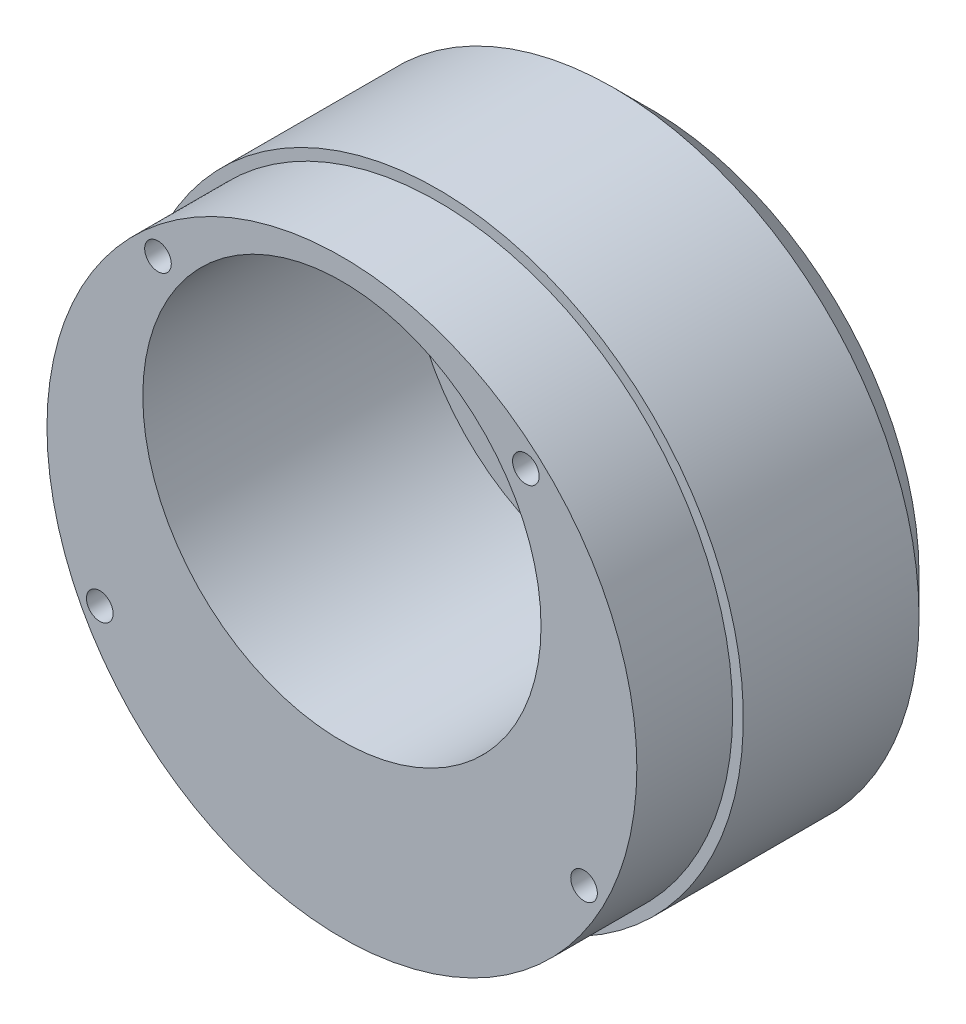
SolidWorks part; units mm, degrees
ref_plane "Спереди" through (0, 0, 0) normal (0, 0, 1) x (1, 0, 0)
ref_plane "Сверху" through (0, 0, 0) normal (0, 1, 0) x (1, 0, 0)
ref_plane "Справа" through (0, 0, 0) normal (1, 0, 0) x (0, 0, -1)
sketch "Sketch1" plane through (0, 0, 0) normal (0, 0, 1) x (1, 0, 0)
  circle A0 centre (0, 0) radius 28.7
  circle A1 centre (0, 0) radius 6.15
  circle A3 centre (0, 7) radius 15.5 construction
  circle A4 centre (15.5, 7) radius 1.65
  circle A5 centre (7.75, -6.4234) radius 1.65
  circle A6 centre (-7.75, -6.4234) radius 1.65
  circle A7 centre (-15.5, 7) radius 1.65
  circle A8 centre (-7.75, 20.4234) radius 1.65
  circle A9 centre (7.75, 20.4234) radius 1.65
  point P20 (0, 7)
  dimension "D1" = 57.4
  dimension "D2" = 12.3
  dimension "D3" = 7
  dimension "D4" = 31
  dimension "D5" = 3.3
  dimension "D6" = 6
extrude "Основа" add sketch "Sketch1" along normal blind 29
sketch "Sketch2" plane through (0, 0, 29) normal (0, 0, 1) x (1, 0, 0)
  circle A0 centre (0, 7) radius 18.7
  dimension "D1" = 37.4
  dimension "D2" = 7
extrude "Посадочное под двигатель" cut sketch "Sketch2" against normal offset from surface (25 mm away) 4 up to face at (28.7, 0, 0)
sketch "Sketch4" plane through (0, 0, 29) normal (0, 0, 1) x (1, 0, 0)
  circle A0 centre (0, 0) radius 27.7
  circle A1 centre (0, 0) radius 28.7
  circle A2 centre (0, 0) radius 28.7 construction
  dimension "D1" = 55.4
extrude "Вырез под внутреннее кольцо подшипника" cut sketch "Sketch4" against normal blind 9
sketch "Sketch5" plane through (0, 0, 29) normal (0, 0, 1) x (1, 0, 0)
  line L0 (0, 7) -> (0, -25.75) construction
  line L1 (-22.74, -12.0811) -> (0, 7) construction
  line L2 (0, 7) -> (-17.2746, 19.0958) construction
  circle A1 centre (0, 7) radius 18.7 construction
  circle A3 centre (-22.74, -12.0811) radius 1.25
  circle A7 centre (-17.2746, 19.0958) radius 1.25
  circle A12 centre (0, 0) radius 25.75 construction
  circle A13 centre (0, 7) radius 18.7 construction
  circle A14 centre (0, -25.75) radius 1.25 construction
  circle A15 centre (17.2746, 19.0958) radius 1.25
  circle A16 centre (22.74, -12.0811) radius 1.25
  dimension "D1" = 51.5
  dimension "D4" = 2.5
  dimension "D2" = 50
  dimension "D3" = 125
extrude "Под шурупы крепления колена" cut sketch "Sketch5" against normal blind 10
chamfer "Chamfer1" distance 3.5 angle 45 1 edges at (28.7, 0, 0)
sketch "Эскиз1" plane through (0, 0, 0) normal (0, 0, -1) x (-1, 0, 0)
  circle A0 centre (-7.75, 20.4234) radius 3
  circle A1 centre (7.75, 20.4234) radius 3
  circle A2 centre (15.5, 7) radius 3
  circle A3 centre (7.75, -6.4234) radius 3
  circle A4 centre (-7.75, -6.4234) radius 3
  circle A5 centre (-15.5, 7) radius 3
  dimension "D1" = 6
extrude "Углубления под шляпки" cut sketch "Эскиз1" against normal blind 2
chamfer "Скругления под шляпки винтов крепления двигателя к стакану" distance 1.5 angle 45 6 edges at (13.85, 7, 2) (6.1, -6.4234, 2) (-9.4, -6.4234, 2) (-17.15, 7, 2) (-9.4, 20.4234, 2) (6.1, 20.4234, 2)
